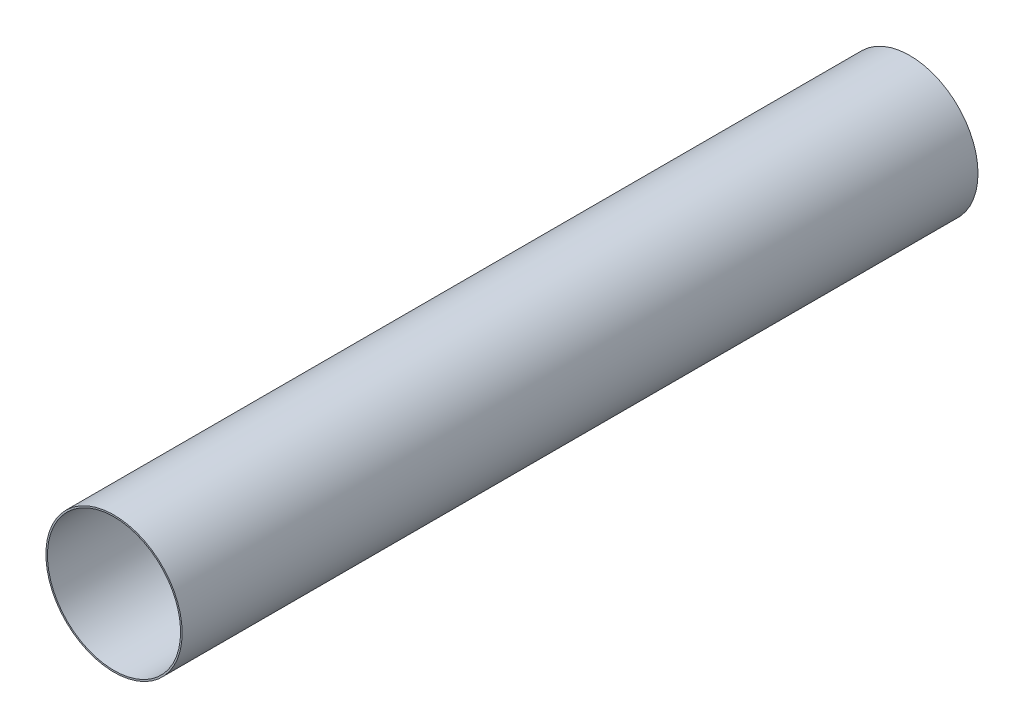
SolidWorks part; units mm, degrees
material "Thornel Mat VMA"
ref_plane "Front Plane" through (0, 0, 0) normal (0, 0, 1) x (1, 0, 0)
ref_plane "Top Plane" through (0, 0, 0) normal (0, 1, 0) x (1, 0, 0)
ref_plane "Right Plane" through (0, 0, 0) normal (1, 0, 0) x (0, 0, -1)
sketch "Sketch1" plane through (0, 0, 0) normal (0, 0, 1) x (1, 0, 0)
  circle A0 centre (0, 0) radius 86.9998
  circle A1 centre (0, 0) radius 84.9998
  dimension "D1" = 169.9997
  dimension "D2" = 173.9997
extrude "Boss-Extrude1" add sketch "Sketch1" along normal mid plane 1016
equation "\"TubeDiameter\"= 6.6929in"
equation "\"D1@Sketch1\"=\"TubeDiameter\""
equation "\"D2@Sketch1\"=\"TubeDiameter\"+4mm"
